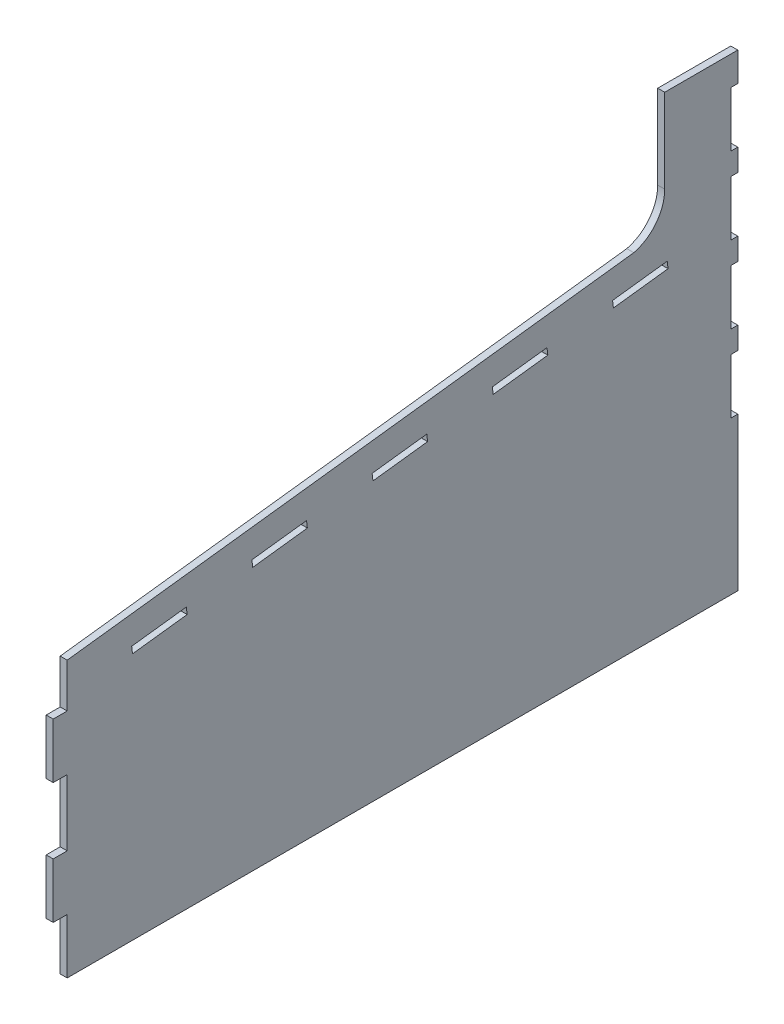
SolidWorks part; units mm, degrees
material "Beech"
ref_plane "Front Plane" through (0, 0, 0) normal (0, 0, 1) x (1, 0, 0)
ref_plane "Top Plane" through (0, 0, 0) normal (0, 1, 0) x (1, 0, 0)
ref_plane "Right Plane" through (0, 0, 0) normal (1, 0, 0) x (0, 0, -1)
sketch "Sketch1" plane through (0, 0, 0) normal (1, 0, 0) x (0, 0, -1)
  line L0 (0, 250) -> (514.5695, 313.1812)
  line L1 (0, 0) -> (609, 0)
  line L2 (0, 0) -> (0, 50)
  line L4 (609, 0) -> (609, 138.97)
  line L6 (609, 258.97) -> (609, 278.97)
  line L7 (609, 425.32) -> (542.65, 425.32)
  line L8 (542.65, 349.09) -> (542.65, 425.32)
  line L9 (0, 250) -> (609, 250) construction
  line L10 (514.5695, 313.1812) -> (609, 324.7758) construction
  line L11 (-12.7, 160) -> (-12.7, 210)
  line L12 (0, 50) -> (-12.7, 50)
  line L14 (0, 100) -> (-12.7, 100)
  line L15 (-12.7, 50) -> (-12.7, 100)
  line L16 (0, 160) -> (-12.7, 160)
  line L18 (0, 210) -> (-12.7, 210)
  line L19 (0, 210) -> (0, 250)
  line L21 (0, 100) -> (0, 160)
  line L23 (609, 398.97) -> (602.65, 398.97)
  line L25 (609, 348.97) -> (602.65, 348.97)
  line L26 (602.65, 398.97) -> (602.65, 348.97)
  line L28 (609, 328.97) -> (602.65, 328.97)
  line L29 (602.65, 328.97) -> (602.65, 278.97)
  line L30 (609, 278.97) -> (602.65, 278.97)
  line L32 (609, 258.97) -> (602.65, 258.97)
  line L33 (602.65, 258.97) -> (602.65, 208.97)
  line L34 (609, 208.97) -> (602.65, 208.97)
  line L36 (609, 188.97) -> (602.65, 188.97)
  line L37 (602.65, 188.97) -> (602.65, 138.97)
  line L38 (609, 138.97) -> (602.65, 138.97)
  line L39 (609, 188.97) -> (609, 208.97)
  line L42 (609, 328.97) -> (609, 348.97)
  line L44 (609, 398.97) -> (609, 425.32)
  arc A0 (514.5695, 313.1812) -> (542.65, 349.09) centre (505.65, 349.09) ccw
  dimension "D4" = 37
  dimension "D1" = 609
  dimension "D2" = 250
  dimension "D3" = 66.35
  dimension "D5" = 7
  dimension "D6" = 175.32
  dimension "D7" = 76.23
  dimension "D8" = 12.7
  dimension "D9" = 50
  dimension "D10" = 50
  dimension "D11" = 2
  dimension "D12" = 40
  dimension "D13" = 6.35
  dimension "D14" = 50
  dimension "D15" = 26.35
  dimension "D17" = 138.97
  dimension "D16" = 4
extrude "Boss-Extrude1" add sketch "Sketch1" along normal blind 6.35
sketch "Sketch2" plane through (6.35, 0, 0) normal (1, 0, 0) x (0, 0, -1)
  line L0 (514.5695, 313.1812) -> (609, 324.7758) construction
  line L1 (609, 0) -> (609, 138.97) construction
  line L2 (514.5695, 313.1812) -> (0, 250) construction
  line L3 (0, 224.4093) -> (609, 299.185) construction
  line L4 (0, 50) -> (0, 0) construction
  line L5 (58.5602, 231.5995) -> (59.3341, 225.2969)
  line L6 (59.3341, 225.2969) -> (108.9614, 231.3903)
  line L7 (108.9614, 231.3903) -> (108.1875, 237.693)
  line L8 (108.1875, 237.693) -> (58.5602, 231.5995)
  line L9 (217.3676, 251.0986) -> (167.7403, 245.0052)
  line L10 (167.7403, 245.0052) -> (168.5142, 238.7025)
  line L11 (168.5142, 238.7025) -> (218.1415, 244.796)
  line L12 (218.1415, 244.796) -> (217.3676, 251.0986)
  line L13 (326.5477, 264.5043) -> (276.9204, 258.4108)
  line L14 (276.9204, 258.4108) -> (277.6942, 252.1081)
  line L15 (277.6942, 252.1081) -> (327.3216, 258.2016)
  line L16 (327.3216, 258.2016) -> (326.5477, 264.5043)
  line L17 (435.7278, 277.9099) -> (386.1005, 271.8164)
  line L18 (386.1005, 271.8164) -> (386.8743, 265.5138)
  line L19 (386.8743, 265.5138) -> (436.5016, 271.6072)
  line L20 (436.5016, 271.6072) -> (435.7278, 277.9099)
  line L21 (544.9078, 291.3155) -> (495.2805, 285.2221)
  line L22 (495.2805, 285.2221) -> (496.0544, 278.9194)
  line L23 (496.0544, 278.9194) -> (545.6817, 285.0129)
  line L24 (545.6817, 285.0129) -> (544.9078, 291.3155)
  dimension "D1" = 25.4
  dimension "D2" = 50
  dimension "D3" = 6.35
  dimension "D4" = 59
extrude "Cut-Extrude1" cut sketch "Sketch2" against normal blind 6.35
